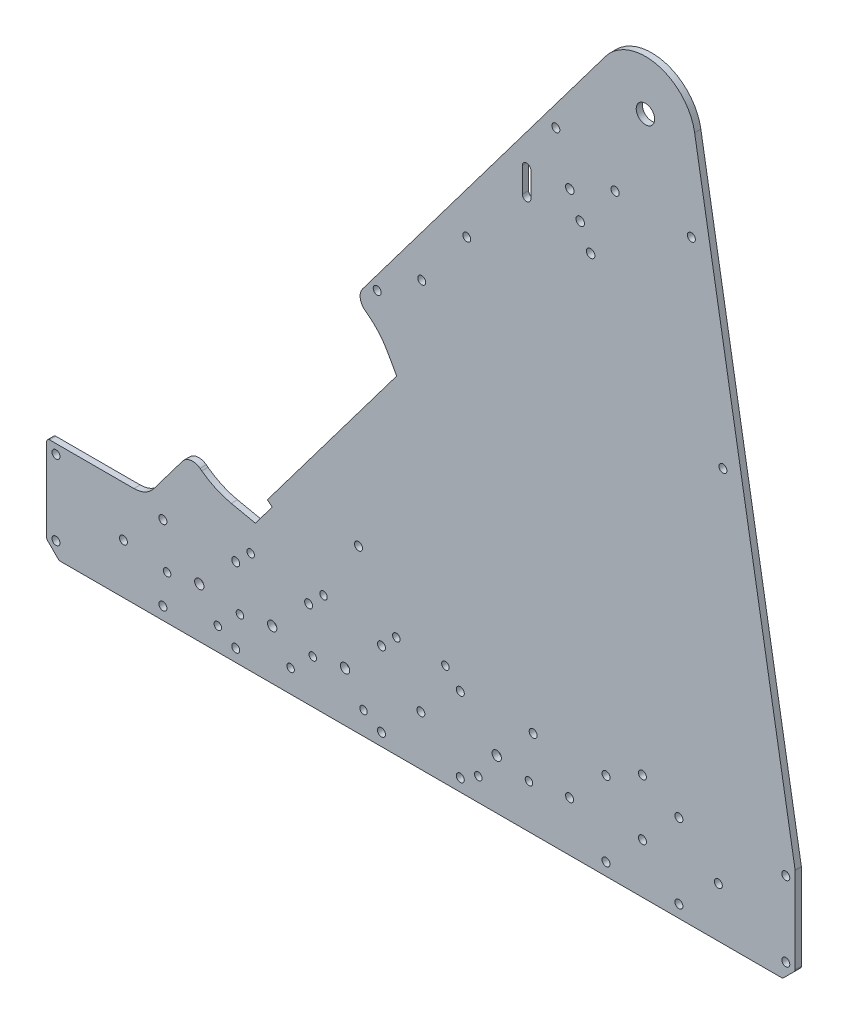
SolidWorks part; units mm, degrees
ref_plane "Front Plane" through (0, 0, 0) normal (0, 0, 1) x (1, 0, 0)
ref_plane "Top Plane" through (0, 0, 0) normal (0, 1, 0) x (1, 0, 0)
ref_plane "Right Plane" through (0, 0, 0) normal (1, 0, 0) x (0, 0, -1)
sketch "Sketch1" plane through (0, 0, 0) normal (0, 0, 1) x (1, 0, 0)
  line L1 (0, 0) -> (381, 0)
  line L2 (0, 0) -> (0, 50.8)
  line L4 (381, 0) -> (381, 50.8)
  line L5 (381, 50.8) -> (329.8374, 350.3513)
  line L6 (0, 50.8) -> (44.463, 50.8)
  line L7 (54.6105, 55.8634) -> (73.025, 80.3327)
  line L9 (112.3265, 79.755) -> (178.1676, 167.245)
  line L11 (157.0275, 191.9556) -> (284.5049, 361.3482)
  line L12 (112.3265, 79.755) -> (114.8634, 77.8458)
  line L13 (114.8634, 77.8458) -> (106.2722, 66.4299)
  line L14 (157.0275, 191.9556) -> (169.7119, 182.4098)
  line L15 (169.7119, 182.4098) -> (178.1676, 167.245)
  line L16 (73.025, 80.3327) -> (85.7094, 70.7869)
  line L17 (85.7094, 70.7869) -> (106.2722, 66.4299)
  line L18 (169.7119, 182.4098) -> (85.7094, 70.7869) construction
  arc A0 (284.5049, 361.3482) -> (329.8374, 350.3513) centre (304.8, 346.075) cw
  arc A1 (44.463, 50.8) -> (54.6105, 55.8634) centre (44.463, 63.5) ccw
  point P11 (50.8, 50.8)
  dimension "D4" = 346.075
  dimension "D7" = 12.7
  dimension "D5" = 25.4
  dimension "D1" = 50.8
  dimension "D2" = 381
  dimension "D3" = 76.2
  dimension "D6" = 50.8
  dimension "D8" = 123.825
  dimension "D9" = 139.7
  dimension "D10" = 15.875
  dimension "D11" = 31.75
  dimension "D12" = 73.025
  dimension "D13" = 3.175
  dimension "D14" = 14.2875
  dimension "D15" = 115
extrude "Boss-Extrude1" add sketch "Sketch1" along normal blind 3.175
sketch "Sketch2" plane through (0, 0, 3.175) normal (0, 0, 1) x (1, 0, 0)
  line L1 (190.5, 50.8) -> (190.5, 0) construction
  line L3 (0, 0) -> (381, 0) construction
  line L5 (0, 6.35) -> (0, 0)
  line L6 (0, 50.8) -> (0, 0) construction
  line L7 (0, 0) -> (6.35, 0)
  line L8 (6.35, 0) -> (0, 6.35)
  line L9 (381, 0) -> (374.65, 0)
  line L10 (374.65, 0) -> (381, 6.35)
  line L11 (381, 6.35) -> (381, 0)
  circle A19 centre (4.7625, 46.0375) radius 2.032
  circle A20 centre (4.7625, 7.9375) radius 2.032
  circle A21 centre (376.2375, 7.9375) radius 2.032
  circle A22 centre (376.2375, 46.0375) radius 2.032
  dimension "D21" = 6.35
  dimension "D27" = 4.064
  dimension "D4" = 46.0375
  dimension "D22" = 6.35
  dimension "D25" = 4.7625
  dimension "D28" = 7.9375
extrude "Cut-Extrude1" cut sketch "Sketch2" against normal up to next
sketch "Sketch5" plane through (0, 0, 3.175) normal (0, 0, 1) x (1, 0, 0)
  line L0 (151.892, 25.4) -> (229.108, 25.4) construction
  line L1 (229.108, 25.4) -> (341.884, 25.4) construction
  circle A0 centre (39.116, 25.4) radius 2.032
  circle A1 centre (59.182, 6.35) radius 2.032
  circle A2 centre (59.182, 44.45) radius 2.032
  circle A3 centre (96.266, 44.45) radius 2.032
  circle A4 centre (133.35, 44.45) radius 2.032
  circle A5 centre (170.434, 44.45) radius 2.032
  circle A6 centre (210.566, 44.45) radius 2.032
  circle A7 centre (210.566, 6.35) radius 2.032
  circle A8 centre (170.434, 6.35) radius 2.032
  circle A9 centre (247.65, 44.45) radius 2.032
  circle A10 centre (266.192, 25.4) radius 2.032
  circle A11 centre (39.116, 25.4) radius 2.286 construction
  circle A12 centre (59.182, 44.45) radius 1.905 construction
  circle A13 centre (59.182, 6.35) radius 1.905 construction
  circle A14 centre (96.266, 44.45) radius 1.905 construction
  circle A15 centre (133.35, 44.45) radius 1.905 construction
  circle A16 centre (170.434, 44.45) radius 1.905 construction
  circle A17 centre (170.434, 6.35) radius 2.159 construction
  circle A18 centre (210.566, 6.35) radius 2.159 construction
  circle A19 centre (210.566, 44.45) radius 1.905 construction
  circle A20 centre (247.65, 44.45) radius 1.905 construction
  circle A21 centre (266.192, 25.4) radius 2.286 construction
  circle A22 centre (77.724, 25.4) radius 2.3813
  circle A23 centre (114.808, 25.4) radius 2.3813
  circle A24 centre (151.892, 25.4) radius 2.3813
  circle A25 centre (229.108, 25.4) radius 2.3813
  circle A26 centre (190.5, 25.4) radius 2.032
  circle A28 centre (303.276, 25.4) radius 2.032
  circle A29 centre (341.884, 25.4) radius 2.032
  circle A30 centre (77.724, 25.4) radius 7.366 construction
  circle A31 centre (114.808, 25.4) radius 7.366 construction
  circle A32 centre (151.892, 25.4) radius 7.366 construction
  circle A33 centre (229.108, 25.4) radius 7.366 construction
  dimension "D1" = 4.064
  dimension "D2" = 4.7625
  dimension "D3" = 37.084
  dimension "D4" = 38.608
  dimension "D5" = 38.608
extrude "Cut-Extrude4" cut sketch "Sketch5" against normal through all
sketch "Sketch6" plane through (0, 0, 3.175) normal (0, 0, 1) x (1, 0, 0)
  line L0 (6.35, 0) -> (374.65, 0) construction
  line L1 (266.192, 25.4) -> (303.276, 25.4) construction
  line L2 (284.734, 6.35) -> (284.734, 44.45) construction
  line L3 (151.892, 25.4) -> (114.808, 25.4) construction
  line L4 (114.808, 25.4) -> (77.724, 25.4) construction
  circle A0 centre (284.734, 44.45) radius 2.032
  circle A1 centre (284.734, 6.35) radius 2.032
  circle A2 centre (321.818, 6.35) radius 2.032
  circle A3 centre (321.818, 44.45) radius 2.032
  circle A4 centre (96.266, 6.35) radius 2.032
  circle A6 centre (303.276, 53.975) radius 2.032
  arc A7 (304.329, 52.3875) -> (302.223, 52.3875) centre (303.276, 53.975) ccw construction
  point P8 (284.734, 25.4)
  point P9 (284.734, 25.4)
  point P28 (96.266, 25.4)
  dimension "D1" = 4.064
  dimension "D2" = 6.35
  dimension "D3" = 37.084
extrude "Cut-Extrude5" cut sketch "Sketch6" against normal through all
sketch "Sketch3" plane through (0, 0, 3.175) normal (0, 0, 1) x (1, 0, 0)
  line L0 (73.025, 80.3327) -> (54.6105, 55.8634) construction
  line L1 (381, 6.35) -> (381, 50.8) construction
  line L2 (6.35, 0) -> (374.65, 0) construction
  line L3 (304.8, 346.075) -> (289.3732, 304.3879) construction
  line L4 (266.2957, 293.7771) -> (289.3732, 304.3879) construction
  line L5 (266.2957, 293.7771) -> (271.6011, 282.2383) construction
  line L6 (271.6011, 282.2383) -> (276.9065, 270.6996) construction
  line L7 (381, 50.8) -> (329.8374, 350.3513) construction
  line L8 (244.3127, 279.4) -> (244.3127, 292.1) construction
  line L9 (0, 50.8) -> (0, 6.35) construction
  line L12 (284.5049, 361.3482) -> (157.0275, 191.9556) construction
  line L13 (242.1537, 279.4) -> (242.1537, 292.1)
  line L14 (246.4717, 279.4) -> (246.4717, 292.1)
  line L15 (190.9415, 215.9) -> (213.8513, 246.3426) construction
  circle A0 centre (304.8, 346.075) radius 4.699
  circle A1 centre (168.275, 200.025) radius 2.032
  circle A2 centre (158.75, 82.55) radius 2.032
  circle A3 centre (289.3732, 304.3879) radius 2.0955
  circle A5 centre (266.2957, 293.7771) radius 2.159
  circle A6 centre (271.6011, 282.2383) radius 2.159
  circle A7 centre (276.9065, 270.6996) radius 2.159
  circle A8 centre (328.1868, 303.4404) radius 2.032
  circle A9 centre (344.223, 209.55) radius 2.032
  circle A12 centre (259.2118, 317.1783) radius 2.032
  arc A26 (242.1537, 279.4) -> (246.4717, 279.4) centre (244.3127, 279.4) ccw
  arc A27 (246.4717, 292.1) -> (242.1537, 292.1) centre (244.3127, 292.1) ccw
  circle A28 centre (213.8513, 246.3426) radius 2.032
  circle A29 centre (190.9415, 215.9) radius 2.032
  point P27 (244.3127, 285.75)
  point P44 (272.3538, 263.8287)
  point P45 (290.2792, 255.289)
  point P46 (317.8147, 278.9734)
  point P47 (275.7376, 282.9582)
  point P48 (296.0609, 254.4396)
  point P49 (304.0369, 280.0808)
  point P50 (312.509, 286.8588)
  point P51 (263.9755, 304.047)
  point P52 (277.1254, 270.6204)
  point P53 (292.2267, 257.6731)
  point P54 (303.3392, 280.2302)
  dimension "D1" = 9.398
  dimension "D3" = 4.064
  dimension "D6" = 4.064
  dimension "D11" = 4.318
  dimension "D10" = 4.191
  dimension "D13" = 4.064
  dimension "D20" = 4.064
  dimension "D18" = 2.159
  dimension "D28" = 12.7
  dimension "D21" = 38.1
  dimension "D19" = 9.525
  dimension "D29" = 4.064
  dimension "D4" = 222.25
  dimension "D5" = 82.55
  dimension "D7" = 25.4
  dimension "D8" = 12.7
  dimension "D9" = 44.45
  dimension "D12" = 12.7
  dimension "D14" = 9.525
  dimension "D15" = 9.525
  dimension "D16" = 95.25
  dimension "D17" = 209.55
  dimension "D22" = 12.7
  dimension "D23" = 53.975
  dimension "D24" = 6.35
  dimension "D25" = 200.025
  dimension "D26" = 168.275
  dimension "D27" = 279.4
  dimension "D30" = 30
  dimension "D31" = 135
  dimension "D32" = 215.9
extrude "Cut-Extrude2" cut sketch "Sketch3" against normal through all
fillet "Fillet1" radius 1.5875 6 edges at (374.65, 0, 1.5875) (381, 6.35, 1.5875) (381, 50.8, 1.5875) (6.35, 0, 1.5875) (0, 6.35, 1.5875) (0, 50.8, 1.5875)
sketch "Sketch4" plane through (0, 0, 0) normal (0, 0, -1) x (-1, 0, 0)
  circle A0 centre (-61.3181, 22.2981) radius 1.905 construction
  circle A1 centre (-87.1313, 11.606) radius 1.905 construction
  circle A2 centre (-98.4021, 22.2981) radius 1.905 construction
  circle A3 centre (-124.2153, 11.606) radius 1.905 construction
  circle A4 centre (-135.4861, 22.2981) radius 1.905 construction
  circle A5 centre (-161.2993, 11.606) radius 1.905 construction
  circle A6 centre (-245.5139, 22.2981) radius 1.905 construction
  circle A7 centre (-219.7007, 11.606) radius 1.905 construction
  circle A8 centre (-202.982, 51.9684) radius 1.905 construction
  circle A9 centre (-178.018, 51.9684) radius 1.905 construction
  circle A10 centre (-140.934, 51.9684) radius 1.905 construction
  circle A11 centre (-103.85, 51.9684) radius 1.905 construction
  circle A12 centre (-61.3181, 22.2981) radius 1.905
  circle A13 centre (-87.1313, 11.606) radius 1.905
  circle A14 centre (-98.4021, 22.2981) radius 1.905
  circle A15 centre (-124.2153, 11.606) radius 1.905
  circle A16 centre (-135.4861, 22.2981) radius 1.905
  circle A17 centre (-161.2993, 11.606) radius 1.905
  circle A18 centre (-245.5139, 22.2981) radius 1.905
  circle A19 centre (-219.7007, 11.606) radius 1.905
  circle A20 centre (-202.982, 51.9684) radius 1.905
  circle A21 centre (-178.018, 51.9684) radius 1.905
  circle A22 centre (-140.934, 51.9684) radius 1.905
  circle A23 centre (-103.85, 51.9684) radius 1.905
extrude "Cut-Extrude3" cut sketch "Sketch4" against normal up to next
fillet "Fillet2" radius 38.1 2 edges at (85.7094, 70.7869, 1.5875) (169.7119, 182.4098, 1.5875)
fillet "Fillet3" radius 6.35 2 edges at (73.025, 80.3327, 1.5875) (157.0275, 191.9556, 1.5875)
